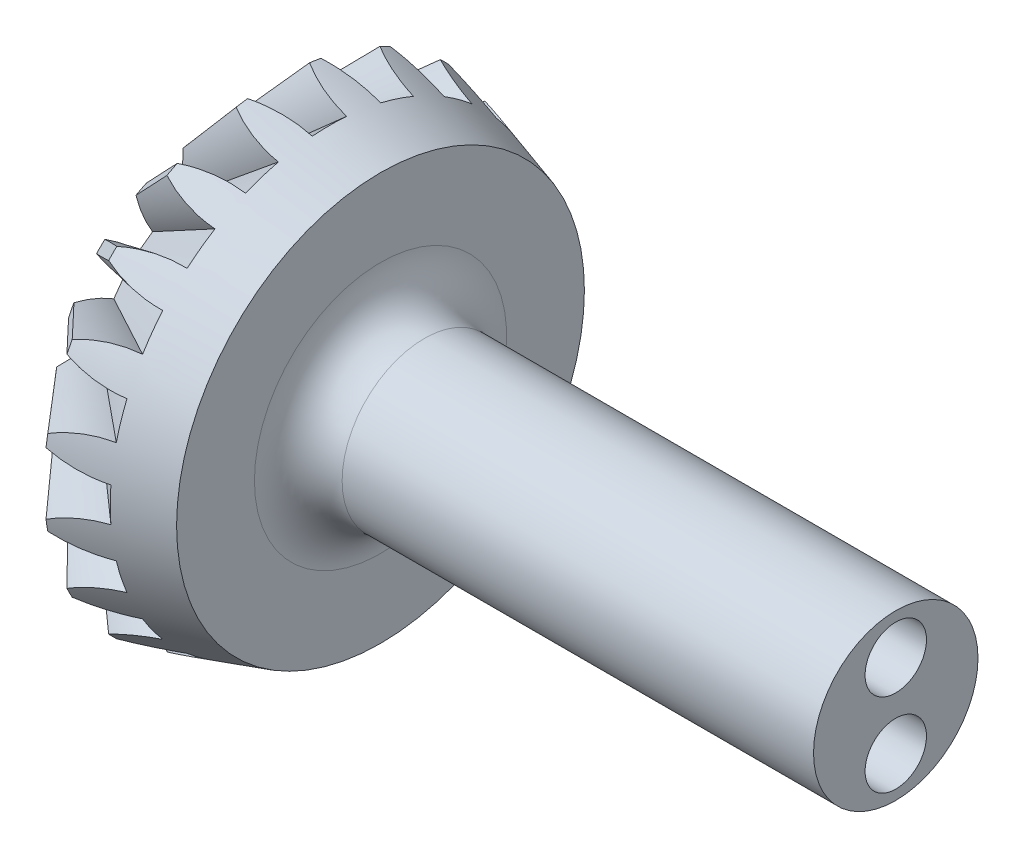
SolidWorks part; units mm, degrees
ref_plane "Front" through (0, 0, 0) normal (0, 0, 1) x (1, 0, 0)
ref_plane "Top" through (0, 0, 0) normal (0, 1, 0) x (1, 0, 0)
ref_plane "Right" through (0, 0, 0) normal (1, 0, 0) x (0, 0, -1)
sketch "Sketch1" plane through (0, 0, 0) normal (0, 0, 1) x (1, 0, 0)
  line L0 (0, 0) -> (14.6, 0) construction
  line L1 (0, 3) -> (14.6, 3)
  line L2 (14.6, 3) -> (14.6, 8)
  line L3 (14.6, 8) -> (7.6, 8)
  line L4 (7.6, 8) -> (7.6, 9.3)
  line L5 (7.6, 9.3) -> (2.9515, 10.7)
  line L6 (2.9515, 10.7) -> (0, 7.3031)
  line L7 (0, 7.3031) -> (0, 3)
  line L8 (5.2757, 10) -> (0, 3.9281) construction
  dimension "D1" = 49.013
  dimension "Overall Length" = 14.6
  dimension "OD" = 21.4
  dimension "For Shaft" = 6
  dimension "Face Width" = 4.5
  dimension "Hub Dia" = 16
  dimension "Hub Width" = 7
  dimension "PD" = 20
revolve "Revolve1" add sketch "Sketch1" angle 360 about L0
sketch "Sketch2" plane through (0, 0, 0) normal (-1, 0, 0) x (0, 0, 1)
  circle A0 centre (0, 0) radius 10
  dimension "Pitch Dia" = 20
sketch "Sketch3" plane through (0, 0, 0) normal (-1, 0, 0) x (0, 0, 1)
  line L0 (-10, 0) -> (10, 0) construction
  point P2 (0, 0)
  dimension "teeth" = 20
sketch "Sketch5" plane through (0, 0, 0) normal (-1, 0, 0) x (0, 0, 1)
  line L0 (0, 0) -> (0, 10.7) construction
  line L1 (0, 0) -> (0.8395, 10.667) construction
  line L2 (0, 0) -> (-0.8395, 10.667) construction
  line L4 (-10, 0) -> (10, 0) construction
  line L5 (-0.4198, 5.3335) -> (0.4198, 5.3335)
  line L6 (0, 0) -> (-3.3065, 10.1763) construction
  line L7 (0, 0) -> (3.3065, 10.1763) construction
  circle A0 centre (0, 0) radius 10.7 construction
  arc A1 (-0.4198, 5.3335) -> (-3.3065, 10.1763) centre (-6.7627, 4.8343) ccw
  arc A2 (0.4198, 5.3335) -> (3.3065, 10.1763) centre (6.7627, 4.8343) cw
  arc A3 (-3.3065, 10.1763) -> (3.3065, 10.1763) centre (0, 0) cw
  point P10 (0, 0)
  dimension "D1" = 9
  dimension "D2" = 36
ref_plane "Plane1" through (5.2757, 0, 0) normal (1, 0, 0) x (0, 0, -1)
sketch "Sketch6" plane through (5.2757, 0, 0) normal (1, 0, 0) x (0, 0, -1)
  line L0 (0, 0) -> (0, 16.05) construction
  line L1 (0, 0) -> (0.8395, 10.667) construction
  line L2 (0, 0) -> (-0.8395, 10.667) construction
  line L3 (0, 0) -> (5.215, 16.05) construction
  line L4 (0, 0) -> (-5.215, 16.05) construction
  line L5 (5.215, 16.05) -> (-5.215, 16.05) construction
  line L6 (0, 10.7) -> (0, 0) construction
  line L7 (-5.215, 16.05) -> (5.215, 16.05)
  circle A0 centre (0, 0) radius 10.7 construction
  arc A1 (-0.7846, 9.9692) -> (-5.215, 16.05) centre (-7.9465, 9.4055) ccw
  arc A2 (0.7846, 9.9692) -> (5.215, 16.05) centre (7.9465, 9.4055) cw
  circle A3 centre (0, 0) radius 10 construction
  arc A4 (0.7846, 9.9692) -> (-0.7846, 9.9692) centre (0, 0) ccw
  dimension "D1" = 9
  dimension "D2" = 36
  dimension "D3" = 16.05
  dimension "D4" = 10.7
loft "Cut-Loft1" cut profiles "Sketch6", "Sketch5" connector at (5.2757, 16.05, -5.215) connector at (0, 10.1763, -3.3065)
pattern_circular "CirPattern1" count 20 over 360 about axis through (0, 0, 0) along (-1, 0, 0) of "Cut-Loft1"
sketch "Sketch7" plane through (0, 0, 0) normal (-1, 0, 0) x (0, 0, 1)
  circle A0 centre (0, 0) radius 10
sketch "Sketch8" plane through (0, 0, 0) normal (0, 1, 0) x (1, 0, 0)
  line L0 (-6.4, 21) -> (-6.4, 6.4) construction
  line L2 (14.6, -8) -> (14.6, 8) construction
  line B0 (-13.6503, 6.4) -> (-17.0063, 9.3515) construction
  line B1 (-17.0063, 9.3515) -> (-15.7, 14) construction
  line B2 (-15.7, 14) -> (-14.4, 14) construction
  line B3 (-14.4, 14) -> (-14.4, 21) construction
  line B4 (-14.4, 21) -> (1.6, 21) construction
  line B5 (1.6, 21) -> (1.6, 14) construction
  line B6 (1.6, 14) -> (2.9, 14) construction
  line B7 (2.9, 14) -> (4.2063, 9.3515) construction
  line B8 (4.2063, 9.3515) -> (0.8503, 6.4) construction
  line B9 (0.8503, 6.4) -> (-13.6503, 6.4) construction
  dimension "D1" = 21
  dimension "D2" = 21
sketch_block_instance "Block2-1"
sketch_block "Block2"
sketch "草图1" plane through (14.6, 0, 0) normal (1, 0, 0) x (0, 0, -1)
  circle A0 centre (0, 0) radius 3
  circle A1 centre (0, 0) radius 8
extrude "切除-拉伸1" cut sketch "草图1" against normal blind 7
ref_plane "基准面1" through (-6.4, 0, 0) normal (1, 0, 0) x (0, 0, -1)
ref_axis "基准轴1" through (7.6, 0, 0) along (-1, 0, 0)
ref_point "点2"
sketch "草图2" plane through (7.6, 0, 0) normal (1, 0, 0) x (0, 0, -1)
  circle A0 centre (0, 0) radius 3.75
  dimension "D1" = 7.5
extrude "凸台-拉伸1" add sketch "草图2" along normal blind 23.5
fillet "圆角2" radius 2 1 edges at (7.6, 0, 3.75) type face fillet first side face at (31.1, 0, -3.75) second side face at (7.6, 0, 3.75)
sketch "草图3" plane through (31.1, 0, 0) normal (1, 0, 0) x (0, 0, -1)
  line L0 (0, 0) -> (0, 1.9) construction
  line L1 (0, 0) -> (0, -1.9) construction
  circle A4 centre (0, 1.9) radius 1.4
  circle A5 centre (0, -1.9) radius 1.4
  dimension "D1" = 1.9
  dimension "D2" = 1.9
  dimension "D3" = 2.8
  dimension "D4" = 2.8
extrude "切除-拉伸2" cut sketch "草图3" against normal blind 5
equation "\"D1@Sketch5\"=(360deg/20)/2"
equation "\"D2@Sketch5\"=(360deg/20)/.5"
equation "\"D1@Sketch6\"=(360deg/\"teeth@Sketch5\")/2"
equation "\"D2@Sketch6\"=(360deg/\"teeth@Sketch5\")/.5"
equation "\"D3@Sketch6\"=\"D4@Sketch6\"*1.5"
